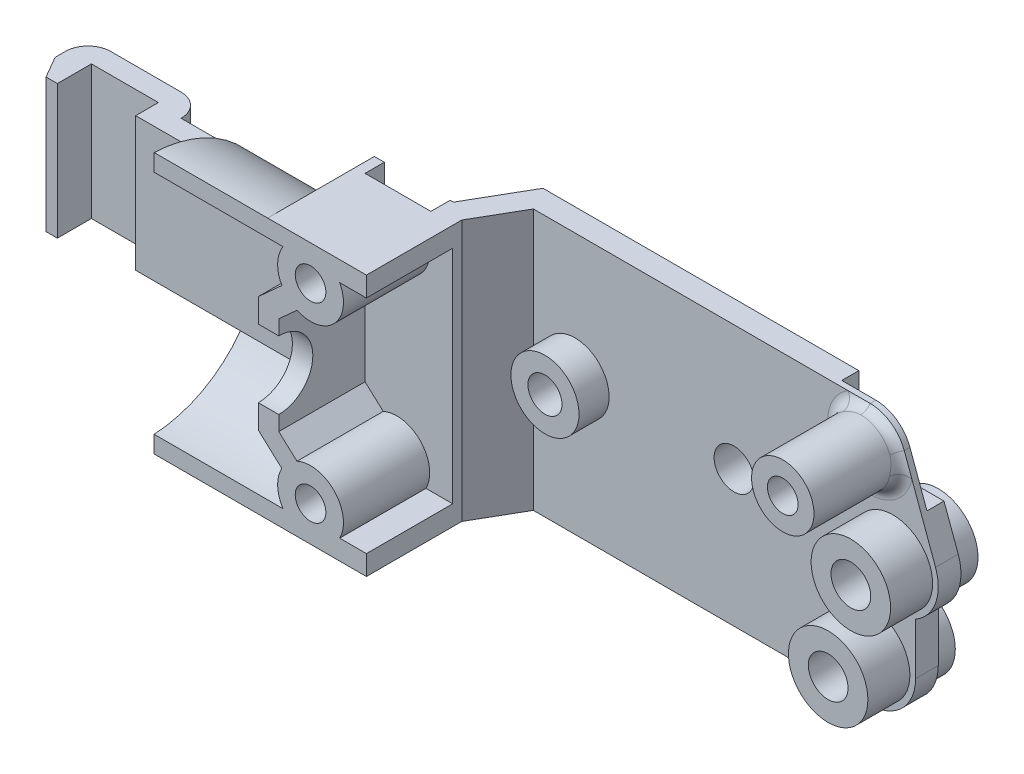
SolidWorks part; units mm, degrees
ref_plane "Front Plane" through (0, 0, 0) normal (0, 0, 1) x (1, 0, 0)
ref_plane "Top Plane" through (0, 0, 0) normal (0, 1, 0) x (1, 0, 0)
ref_plane "Right Plane" through (0, 0, 0) normal (1, 0, 0) x (0, 0, -1)
sketch "Sketch1" plane through (0, 0, 0) normal (0, 0, 1) x (1, 0, 0)
  line L0 (-4.567, -11.8) -> (25.103, -11.8)
  line L1 (29.103, -7.8) -> (29.103, -3.2641)
  line L2 (28.1084, 9.0988) -> (30.8598, 1.5735)
  line L3 (25.103, 11.2) -> (-4.567, 11.2)
  line L4 (29.103, -7.8) -> (29.103, -3.2641) construction
  line L9 (999.5524, 0.2) -> (-4.567, 0.2) construction
  line L10 (-4.567, 11.2) -> (-4.567, -11.8)
  arc A0 (29.103, -3.2641) -> (30.8598, 1.5735) centre (27.103, 0.2) ccw
  circle A2 centre (-0.897, 0.2) radius 1.5
  circle A3 centre (13.103, 0.2) radius 1.75
  circle A4 centre (27.103, 0.2) radius 1.75
  circle A5 centre (25.103, -7.8) radius 1.75
  arc A6 (25.103, -11.8) -> (29.103, -7.8) centre (25.103, -7.8) ccw
  circle A7 centre (25.103, 8) radius 1.35
  arc A9 (25.103, 11.2) -> (28.1084, 9.0988) centre (25.103, 8) cw
  circle A12 centre (-0.897, 0.2) radius 1.5 construction
  point P0 (31.103, 0.2)
  dimension "D9" = 3.5
  dimension "D10" = 3.5
  dimension "D11" = 3
  dimension "D12" = 3.5
  dimension "D13" = 2.7
  dimension "D14" = 4
  dimension "D15" = 3.2
  dimension "D19" = 4
  dimension "D3" = 35.67
  dimension "D4" = 14
  dimension "D7" = 12
  dimension "D8" = 2
  dimension "D18" = 23
  dimension "D20" = 8
  dimension "D21" = 7.8
extrude "Boss-Extrude1" add sketch "Sketch1" along normal blind 2 contours L10 L0 A6 L1 A0 L2 A9 L3 | A3 | A7 | A4 | A5
ref_plane "Plane1" through (0, -0.3, 0) normal (0, 1, 0) x (-1, 0, 0)
sketch "Sketch4" plane through (0, 0, 2) normal (0, 0, 1) x (1, 0, 0)
  circle A0 centre (27.103, 0.2) radius 3.5
  circle A1 centre (27.103, 0.2) radius 1.75 construction
  circle A2 centre (27.103, 0.2) radius 1.75
  circle A3 centre (25.103, -7.8) radius 3.5
  circle A4 centre (25.103, -7.8) radius 1.75 construction
  circle A5 centre (25.103, -7.8) radius 1.75
  dimension "D1" = 7
  dimension "D2" = 7
extrude "Boss-Extrude3" add sketch "Sketch4" along normal offset from surface (3.7 mm away) 3.7 up to face at (28.853, 0.2, 2) offset beyond the face yes
sketch "Sketch3" plane through (0, 0, 0) normal (0, 0, -1) x (-1, 0, 0)
  circle A0 centre (-25.103, -7.8) radius 3.5
  circle A1 centre (-25.103, -7.8) radius 1.75 construction
  circle A2 centre (-25.103, -7.8) radius 1.75
  circle A3 centre (-27.103, 0.2) radius 1.75 construction
  circle A4 centre (-13.103, 0.2) radius 1.75 construction
  circle A5 centre (-27.103, 0.2) radius 1.75
  circle A6 centre (-13.103, 0.2) radius 1.75
  circle A7 centre (-27.103, 0.2) radius 3.5
  circle A8 centre (-13.103, 0.2) radius 3.5
  dimension "D1" = 7
extrude "Boss-Extrude4" add sketch "Sketch3" along normal offset from surface (2 mm away) 7.7 up to face at (28.853, 0.2, 5.7)
sketch "Sketch5" plane through (0, -0.3, 0) normal (0, 1, 0) x (1, 0, 0)
  line L0 (-6.8764, -6.8) -> (-6.8764, -6)
  line L1 (-6.8764, -6.8) -> (-34.8, -6.8)
  line L2 (-34.8, -6.8) -> (-34.8, -4.8)
  line L3 (-34.8, -4.8) -> (-40.703, -4.8)
  line L4 (-40.703, -4.8) -> (-40.703, -7.8)
  line L5 (-40.703, -7.8) -> (-41.703, -7.8)
  line L6 (-41.703, -7.8) -> (-42.8, -5.9)
  line L7 (-42.8, -5.9) -> (-42.8, -3)
  line L9 (-42.8, -3) -> (-32.6, -3)
  line L10 (-32.6, -3) -> (-32.6, -5)
  line L11 (-32.6, -5) -> (-8.6085, -5)
  line L12 (-4.567, 0) -> (-5.7217, 0)
  line L13 (-4.567, -2) -> (-4.567, 0) construction
  line L14 (-4.567, -2) -> (-4.567, 0)
  line L15 (-6.8764, -6) -> (-4.567, -2)
  line L16 (-5.7217, 0) -> (-8.6085, -5)
  line L17 (25.103, 0) -> (-4.567, 0) construction
  dimension "D1" = 2
  dimension "D2" = 3
  dimension "D3" = 1
  dimension "D4" = 1.9
  dimension "D5" = 1.8
  dimension "D6" = 120
  dimension "D7" = 5
  dimension "D8" = 2
  dimension "D9" = 1.8
  dimension "D10" = 34.8
  dimension "D11" = 2.2
  dimension "D12" = 8
  dimension "D13" = 1
  dimension "D14" = 120
extrude "Boss-Extrude5" add sketch "Sketch5" along normal mid plane 11.8
fillet "Fillet1" radius 2 2 edges at (-32.6, -0.3, 3) (-42.8, -0.3, 3)
sketch "Sketch6" plane through (0, 0, 2) normal (0, 0, 1) x (1, 0, 0)
  circle A0 centre (25.103, 8) radius 1.35 construction
  circle A1 centre (25.103, 8) radius 1.35
  circle A2 centre (25.103, 8) radius 2.75
  dimension "D1" = 5.5
extrude "Boss-Extrude6" add sketch "Sketch6" along normal blind 7.7
sketch "Sketch8" plane through (0, 0, 2) normal (0, 0, 1) x (1, 0, 0)
  circle A0 centre (-0.897, 0.2) radius 3
  circle A1 centre (-0.897, 0.2) radius 1.5 construction
  circle A2 centre (-0.897, 0.2) radius 1.5
  dimension "D1" = 6
extrude "Boss-Extrude7" add sketch "Sketch8" along normal blind 2.65
sketch "Sketch9" plane through (0, -0.3, 0) normal (0, -1, 0) x (1, 0, 0)
  line L0 (-5.7217, 0) -> (-8.6085, 5) construction
  line L1 (-4.567, 0) -> (-5.7217, 0) construction
  line L2 (-6.8764, 6) -> (-4.567, 2) construction
  line L3 (-4.567, 2) -> (-4.567, 0) construction
  line L4 (-6.8764, 6.8) -> (-6.8764, 6) construction
  line L5 (-5.7217, 0) -> (-8.6085, 5)
  line L6 (-4.567, 0) -> (-5.7217, 0)
  line L7 (-6.8764, 6) -> (-4.567, 2)
  line L8 (-4.567, 2) -> (-4.567, 0)
  line L9 (-6.8764, 6.8) -> (-6.8764, 6)
  line L10 (-8.6085, 5) -> (-8.6085, 6.8)
  line L11 (-34.8, 6.8) -> (-6.8764, 6.8) construction
  line L12 (-8.6085, 6.8) -> (-6.8764, 6.8)
extrude "Boss-Extrude10" add sketch "Sketch9" along normal mid plane 23
sketch "Sketch10" plane through (0, 0, 5) normal (0, 0, -1) x (-1, 0, 0)
  line L0 (25.5764, -11.8) -> (6.8764, -11.8)
  line L1 (6.8764, -11.8) -> (6.8764, -10.05)
  line L2 (6.8764, -10.05) -> (9.2304, -10.05)
  line L3 (12.9925, -6.0579) -> (14.597, -4.6025)
  line L4 (14.597, -4.6025) -> (14.597, 4.0025)
  line L5 (16.397, 4.8) -> (16.397, -5.4)
  line L6 (16.397, -5.4) -> (14.3251, -7.2792)
  line L7 (14.0708, -10.5) -> (25.5764, -10.5)
  line L8 (25.5764, -10.5) -> (25.5764, -11.8)
  line L9 (25.5764, 9.9) -> (25.5764, 11.2)
  line L10 (14.0708, 9.9) -> (25.5764, 9.9)
  line L11 (16.397, 4.8) -> (14.3251, 6.6792)
  line L12 (-8.6455, -0.3) -> (-5.3863, -0.3) construction
  line L13 (-25.103, 11.2) -> (4.567, 11.2) construction
  line L14 (12.9925, 5.4579) -> (14.597, 4.0025)
  line L15 (6.8764, 9.45) -> (9.2304, 9.45)
  line L16 (6.8764, 11.2) -> (6.8764, 9.45)
  line L17 (25.5764, 11.2) -> (6.8764, 11.2)
  line L20 (8.6085, 11.2) -> (6.8764, 11.2) construction
  line L21 (8.6085, -11.8) -> (6.8764, -11.8) construction
  line L22 (4.567, -11.8) -> (-25.103, -11.8) construction
  line L23 (6.8764, 11.2) -> (6.8764, -11.8) construction
  line L24 (6.8764, 11.2) -> (6.8764, -11.8) construction
  line L25 (16.397, 4.8) -> (16.397, 2.7) construction
  arc A0 (9.2304, -10.05) -> (12.9925, -6.0579) centre (11.797, -8.7) cw
  arc A1 (14.3251, -7.2792) -> (14.0708, -10.5) centre (11.797, -8.7) cw
  arc A2 (14.3251, 6.6792) -> (14.0708, 9.9) centre (11.797, 8.1) ccw
  arc A3 (9.2304, 9.45) -> (12.9925, 5.4579) centre (11.797, 8.1) ccw
  circle A4 centre (11.797, 8.1) radius 1.35
  circle A5 centre (11.797, -8.7) radius 1.35
  dimension "D1" = 2.9
  dimension "D14" = 2.7
  dimension "D11" = 10.9
  dimension "D2" = 1.3
  dimension "D3" = 1.8
  dimension "D4" = 18.7
  dimension "D5" = 1.8
  dimension "D6" = 10.2
  dimension "D7" = 1.3
  dimension "D8" = 1.75
  dimension "D9" = 3.1
  dimension "D10" = 3.1
  dimension "D12" = 1.8
extrude "Boss-Extrude11" add sketch "Sketch10" against normal offset from surface (9.4 mm away) 7.6 up to face at (-14.7233, -0.3, 6.8) offset beyond the face yes
sketch "Sketch11" plane through (0, 0, 5) normal (0, 0, -1) x (-1, 0, 0)
  line L0 (25.5764, 11.2) -> (8.6085, 11.2) construction
  line L1 (8.6085, -11.8) -> (17.0924, -11.8)
  line L2 (8.6085, -11.8) -> (8.6085, 11.2)
  line L3 (8.6085, 11.2) -> (17.0924, 11.2)
  line L4 (17.0924, -11.8) -> (17.0924, 11.2)
  circle A0 centre (11.797, 8.1) radius 1.35 construction
  circle A1 centre (11.797, -8.7) radius 1.35 construction
  circle A2 centre (11.797, 8.1) radius 1.35
  circle A3 centre (11.797, -8.7) radius 1.35
extrude "Boss-Extrude12" add sketch "Sketch11" against normal up to surface (1.8 mm away) up to face at (-10.3321, -0.3, 6.8)
sketch "Sketch13" plane through (0, 0, 0) normal (0, 0, -1) x (-1, 0, 0)
  line L0 (-29.607, 5) -> (-25.103, 5)
  line L1 (-28.1084, 9.0988) -> (-30.8598, 1.5735) construction
  line L2 (-22.103, 8) -> (-22.103, 11.2)
  line L3 (-25.103, 11.2) -> (5.7217, 11.2) construction
  line L4 (-28.1084, 9.0988) -> (-29.607, 5)
  line L5 (-25.103, 11.2) -> (-22.103, 11.2)
  arc A0 (-25.103, 5) -> (-22.103, 8) centre (-25.103, 8) ccw
  circle A1 centre (-25.103, 8) radius 1.35 construction
  arc A2 (-25.103, 11.2) -> (-28.1084, 9.0988) centre (-25.103, 8) ccw construction
  arc A3 (-25.103, 11.2) -> (-28.1084, 9.0988) centre (-25.103, 8) ccw
  dimension "D1" = 3
extrude "Cut-Extrude3" cut sketch "Sketch13" against normal blind 1.5
fillet "Fillet2" radius 1 1 edges at (27.853, 8, 2)
sketch "Sketch14" plane through (-25.5764, 0, 0) normal (-1, 0, 0) x (0, 0, 1)
  line L2 (5, 5.6) -> (6.8, 5.6) construction
  line L3 (14.4, 8.1579) -> (14.4, -49991.8421) construction
  line L7 (14.4, 9.6956) -> (14.4, 11.2)
  line L8 (6.8, 5.6) -> (5, 5.6)
  line L9 (5, -6.2) -> (6.8, -6.2)
  line L10 (14.4, -10.2956) -> (14.4, -11.8)
  arc A0 (14.4, 11.2) -> (5, 5.6) centre (14.883, -0.3) ccw
  arc A1 (14.4, 9.6956) -> (6.8, 5.6) centre (14.883, -0.3) ccw
  arc A2 (5, -6.2) -> (14.4, -11.8) centre (14.883, -0.3) ccw
  arc A3 (6.8, -6.2) -> (14.4, -10.2956) centre (14.883, -0.3) ccw
  dimension "D1" = 1.8
  dimension "D2" = 1.5044
extrude "Boss-Extrude14" add sketch "Sketch14" against normal up to vertex (11.5056 mm away) up to point (-14.0708, 9.9, 6.8)
sketch "Sketch12" plane through (0, 0, 5) normal (0, 0, -1) x (-1, 0, 0)
  line L0 (8.897, -11.8) -> (8.897, -8.7)
  line L1 (8.6085, -11.8) -> (25.5764, -11.8) construction
  line L2 (14.697, -8.7) -> (14.697, -11.8)
  line L3 (14.697, -11.8) -> (8.897, -11.8)
  arc A0 (8.897, -8.7) -> (14.697, -8.7) centre (11.797, -8.7) cw
  arc A1 (12.9925, -6.0579) -> (9.2304, -10.05) centre (11.797, -8.7) ccw construction
extrude "Cut-Extrude1" cut sketch "Sketch12" against normal blind 1.7
mirror "Mirror1" about plane through (0, -0.3, 0) normal (0, 1, 0) of "Cut-Extrude1"
sketch "Sketch17" plane through (0, 0, 5) normal (0, 0, -1) x (-1, 0, 0)
  line L0 (15.197, 11.2) -> (15.197, 6.7766)
  line L1 (25.5764, 11.2) -> (14.697, 11.2) construction
  line L2 (15.197, 6.7766) -> (16.197, 6.7766)
  line L3 (16.197, 6.7766) -> (16.197, 11.2)
  line L4 (15.197, 11.2) -> (16.197, 11.2)
  line L5 (14.697, 11.2) -> (14.697, 8.1) construction
  dimension "D1" = 0.5
  dimension "D2" = 1
extrude "Boss-Extrude15" add sketch "Sketch17" against normal up to surface (9.4 mm away) up to face at (-19.0676, 7.7657, 6.9034)
sketch "Sketch18" plane through (-25.5764, 0, 0) normal (-1, 0, 0) x (0, 0, 1)
  line L0 (14.4, 11.2) -> (5, 11.2) construction
  line L3 (14.4, 11.2) -> (5, 11.2)
  line L4 (5, 11.2) -> (5, 5.6)
  line L5 (5, 5.6) -> (5, 9.9) construction
  arc A0 (14.4, 11.2) -> (5, 5.6) centre (14.883, -0.3) ccw
  arc A2 (9.5498, 9.9) -> (5, 5.6) centre (14.883, -0.3) ccw construction
extrude "Cut-Extrude5" cut sketch "Sketch18" against normal blind 10
sketch "Sketch19" plane through (0, 0, 5) normal (0, 0, -1) x (-1, 0, 0)
  line L0 (14.697, -11.8) -> (25.5764, -11.8) construction
  line L1 (15.197, -11.8) -> (16.697, -11.8)
  line L2 (15.197, -11.8) -> (15.197, -5.8923)
  line L3 (15.197, -5.8923) -> (16.697, -5.8923)
  line L4 (16.697, -11.8) -> (16.697, -5.8923)
  line L5 (14.697, -11.8) -> (14.697, -8.7) construction
  dimension "D1" = 0.5
  dimension "D2" = 1.5
extrude "Boss-Extrude16" add sketch "Sketch19" against normal up to surface (9.4 mm away) up to face at (-19.0355, -8.5046, 7.0809)
sketch "Sketch20" plane through (-25.5764, 0, 0) normal (-1, 0, 0) x (0, 0, 1)
  line L0 (14.4, -11.8) -> (5, -11.8) construction
  line L1 (14.4, -11.8) -> (5, -11.8)
  line L2 (5, -6.2) -> (5, -11.8)
  arc A0 (5, -6.2) -> (14.4, -11.8) centre (14.883, -0.3) ccw
  arc A1 (5, -6.2) -> (9.5498, -10.5) centre (14.883, -0.3) ccw construction
extrude "Cut-Extrude6" cut sketch "Sketch20" against normal up to surface (10 mm away) up to face at (-15.5764, 9.7295, 7.8973)
sketch "Sketch21" plane through (-16.397, 0, 0) normal (-1, 0, 0) x (0, 0, 1)
  line L0 (14.4, 4.8) -> (14.4, -5.4) construction
  circle A0 centre (14.4, -0.3) radius 3
  dimension "D1" = 6
extrude "Cut-Extrude7" cut sketch "Sketch21" against normal up to next
sketch "Sketch22" plane through (0, -11.8, 0) normal (0, -1, 0) x (1, 0, 0)
  line L0 (0.812, 0) -> (3.5255, -4.7)
  line L1 (-5.7217, 0) -> (25.103, 0) construction
  line L2 (8.7217, -4.7) -> (11.4352, 0)
  line L3 (9.603, 0) -> (16.603, 0) construction
  line L4 (0.812, 0) -> (4.6236, 0)
  line L5 (4.6236, -3.2) -> (4.6236, 0)
  line L6 (7.6236, 0) -> (11.4352, 0)
  line L7 (7.6236, 0) -> (7.6236, -3.2)
  arc A0 (3.5255, -4.7) -> (8.7217, -4.7) centre (6.1236, -3.2) ccw
  arc A1 (4.6236, -3.2) -> (7.6236, -3.2) centre (6.1236, -3.2) ccw
  point P11 (6.1236, -6.2)
  dimension "D2" = 3
  dimension "D3" = 6.2
  dimension "D5" = 1.5
  dimension "D1" = 120
  dimension "D4" = 13
extrude "Boss-Extrude17" add sketch "Sketch22" against normal blind 2
